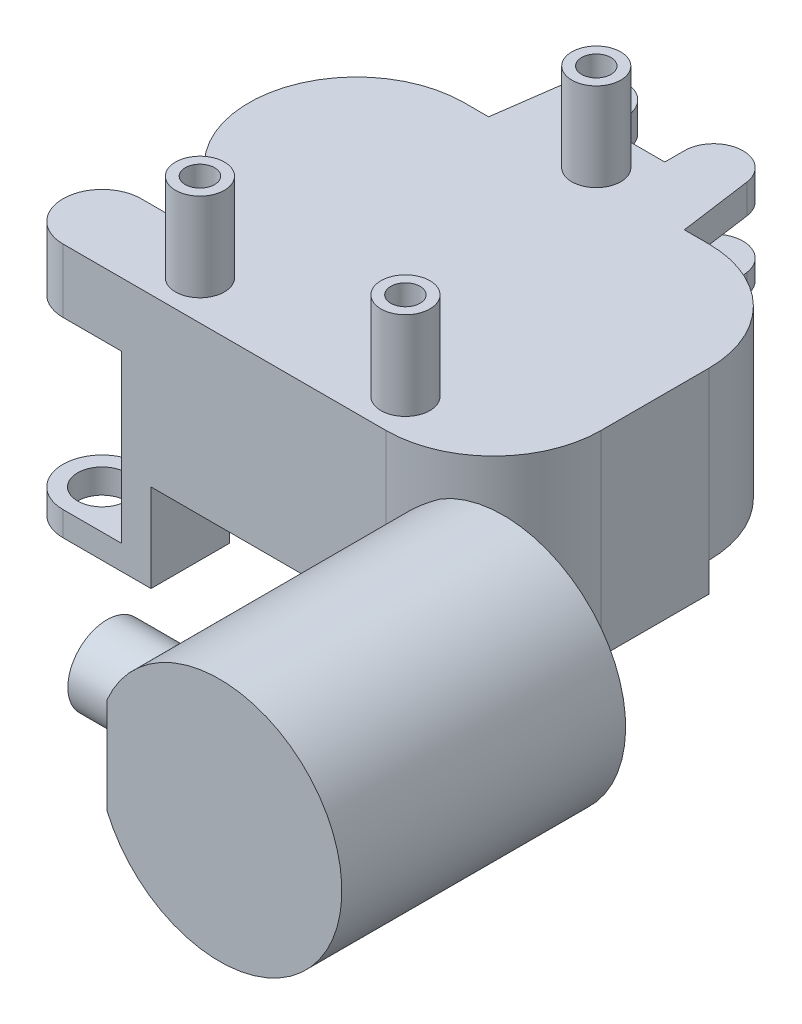
SolidWorks part; units mm, degrees
ref_plane "Front Plane" through (0, 0, 0) normal (0, 0, 1) x (1, 0, 0)
ref_plane "Top Plane" through (0, 0, 0) normal (0, 1, 0) x (1, 0, 0)
ref_plane "Right Plane" through (0, 0, 0) normal (1, 0, 0) x (0, 0, -1)
sketch "Sketch1" plane through (0, 0, 0) normal (0, 1, 0) x (1, 0, 0)
  line L0 (0, 0) -> (-101.2967, 0) construction
  line L6 (-11, 16.5) -> (-36, 16.5)
  line L7 (-41, -4.298) -> (-41, -16.5)
  line L8 (-41, -16.5) -> (-11, -16.5)
  line L10 (0, -5.5) -> (0, 5.5)
  arc A5 (0, 5.5) -> (-11, 16.5) centre (-11, 5.5) ccw
  arc A6 (-36, 16.5) -> (-41, -4.298) centre (-36, 5.5) ccw
  arc A7 (-11, -16.5) -> (0, -5.5) centre (-11, -5.5) ccw
  point P13 (0, 0)
  dimension "D1" = 11
  dimension "D4" = 41
  dimension "D5" = 11
  dimension "D2" = 36
  dimension "D3" = 33
extrude "Boss-Extrude1" add sketch "Sketch1" along normal blind 17
sketch "Sketch2" plane through (0, 17, 0) normal (0, 1, 0) x (1, 0, 0)
  line L0 (-33.5, 16.5) -> (-32.4715, 23.9123)
  line L2 (-26.5, 23.5) -> (-26.5, 21.5)
  line L3 (-26.5, 21.5) -> (-20.5, 21.5)
  line L4 (-20.5, 21.5) -> (-20.5, 23.5)
  line L5 (-14.5285, 23.9123) -> (-13.5, 16.5)
  line L6 (-33.5, 16.5) -> (-13.5, 16.5)
  line L10 (-11, 16.5) -> (-36, 16.5) construction
  arc A0 (-32.4715, 23.9123) -> (-26.5, 23.5) centre (-29.5, 23.5) cw
  arc A1 (-20.5, 23.5) -> (-14.5285, 23.9123) centre (-17.5, 23.5) cw
  point P3 (-23.5, 16.5)
  point P25 (-23.5, 21.5)
  dimension "D1" = 3
  dimension "D2" = 2
  dimension "D3" = 5
  dimension "D4" = 6
  dimension "D5" = 20
  dimension "D6" = 13.5
extrude "Boss-Extrude2" add sketch "Sketch2" against normal blind 10
ref_plane "Plane1" through (0, 0, 44.5) normal (0, 0, 1) x (1, 0, 0)
sketch "Sketch5" plane through (0, 0, 44.5) normal (0, 0, 1) x (1, 0, 0)
  line L0 (0, 17) -> (-11, 17) construction
  line L1 (-11.5, 6.899) -> (-11.5, -2.899)
  arc A0 (-11.5, -2.899) -> (-11.5, 6.899) centre (0, 2) ccw
  dimension "D2" = 12.5
  dimension "D1" = 15
  dimension "D3" = 11.5
extrude "Boss-Extrude3" add sketch "Sketch5" against normal blind 29
sketch "Sketch6" plane through (-11.5, 0, 0) normal (-1, 0, 0) x (0, 0, 1)
  line L0 (44.5, 6.899) -> (44.5, -2.899) construction
  line L4 (18.0627, 2) -> (42.4878, 2) construction
  line L5 (15.5, -10.5) -> (44.5, -10.5) construction
  line L6 (44.5, 14.5) -> (15.5, 14.5) construction
  circle A0 centre (36.5, 2) radius 4
  dimension "D1" = 8
  dimension "D2" = 8
extrude "Boss-Extrude4" add sketch "Sketch6" along normal blind 8
sketch "Sketch7" plane through (0, 17, 0) normal (0, 1, 0) x (1, 0, 0)
  line L0 (-44, -8.5) -> (-35, -8.5)
  line L2 (-35, -16.5) -> (-44, -16.5)
  line L3 (-35, -8.5) -> (-35, -16.5)
  line L4 (-41, -4.298) -> (-41, -16.5) construction
  line L5 (-41, -16.5) -> (-11, -16.5) construction
  arc A0 (-44, -8.5) -> (-44, -16.5) centre (-44, -12.5) ccw
  dimension "D1" = 4
  dimension "D3" = 3
  dimension "D2" = 13
extrude "Boss-Extrude5" add sketch "Sketch7" against normal blind 26
sketch "Sketch11" plane through (0, 17, 0) normal (0, 1, 0) x (1, 0, 0)
  line L0 (-11, 16.5) -> (-13.5, 16.5) construction
  line L1 (-23.5, 27.1588) -> (-23.5, -9.7895) construction
  circle A0 centre (-23.5, 17.5) radius 2.5
  circle A1 centre (-34, -12.5) radius 2.5
  circle A2 centre (-13, -12.5) radius 2.5
  dimension "D2" = 30
  dimension "D3" = 21
  dimension "D4" = 5
  dimension "D1" = 1
extrude "Boss-Extrude6" add sketch "Sketch11" along normal blind 9
sketch "Sketch13" plane through (0, 0, 0) normal (0, -1, 0) x (1, 0, 0)
  line L0 (-11, -5.5) -> (0, -5.5)
  line L1 (0, -5.5) -> (0, 5.5)
  arc A0 (0, 5.5) -> (-11, -5.5) centre (-11, 5.5) ccw
extrude "Boss-Extrude8" add sketch "Sketch13" along normal blind 3
sketch "Sketch9" plane through (0, 0, 0) normal (0, -1, 0) x (1, 0, 0)
  line L0 (-25, -16.5) -> (-25, -5.5)
  line L1 (-11, -16.5) -> (-36, -16.5) construction
  line L2 (-25, -16.5) -> (-36, -16.5)
  arc A0 (-25, -5.5) -> (-36, -16.5) centre (-36, -5.5) ccw
extrude "Cut-Extrude1" cut sketch "Sketch9" against normal blind 3
sketch "Sketch12" plane through (0, 0, 0) normal (0, -1, 0) x (1, 0, 0)
  circle A0 centre (-36, -5.5) radius 5
  dimension "D1" = 10
extrude "Boss-Extrude7" add sketch "Sketch12" against normal blind 5 draft 45 from offset 2 draft outward yes
sketch "Sketch10" plane through (0, 0, 16.5) normal (0, 0, 1) x (1, 0, 0)
  line L1 (-48, 10.5) -> (-38, 10.5)
  line L2 (-48, 10.5) -> (-48, -6.5)
  line L3 (-48, -6.5) -> (-38, -6.5)
  line L4 (-38, 10.5) -> (-38, -6.5)
  line L6 (-48, 17) -> (-48, -9) construction
  line L7 (-44, 17) -> (-11, 17) construction
  line L8 (-48, -9) -> (-44, -9) construction
  dimension "D1" = 6.5
  dimension "D2" = 2.5
  dimension "D3" = 10
extrude "Cut-Extrude2" cut sketch "Sketch10" against normal blind 9.2
sketch "Sketch14" plane through (0, 0, 0) normal (1, 0, 0) x (0, 0, -1)
  line L1 (26.5, 9) -> (1.5, 9)
  line L2 (26.5, 9) -> (26.5, 14)
  line L3 (26.5, 14) -> (1.5, 14)
  line L4 (1.5, 9) -> (1.5, 14)
  line L5 (26.5, 9) -> (1.5, 14) construction
  line L6 (26.5, 14) -> (1.5, 9) construction
  line L7 (16.5, 17) -> (23.9123, 17) construction
  line L9 (26.5, 7) -> (26.5, 17) construction
  point P0 (14, 11.5)
  dimension "D1" = 3
  dimension "D2" = 5
  dimension "D3" = 25
extrude "Cut-Extrude3" cut sketch "Sketch14" against normal through all from vertex starting at point (-13.5, 7, -16.5)
sketch "Sketch15" plane through (-19.5, 0, 0) normal (-1, 0, 0) x (0, 0, 1)
  circle A0 centre (36.5, 2) radius 2.5
  dimension "D1" = 5
extrude "Cut-Extrude4" cut sketch "Sketch15" against normal up to surface (8 mm away) contours A0 up to face at (-11.5, -2, 36.5)
sketch "Sketch16" plane through (0, 26, 0) normal (0, 1, 0) x (1, 0, 0)
  circle A0 centre (-23.5, 17.5) radius 1.5
  circle A1 centre (-34, -12.5) radius 1.5
  circle A2 centre (-13, -12.5) radius 1.5
  dimension "D1" = 3
extrude "Cut-Extrude5" cut sketch "Sketch16" against normal offset from surface (6 mm away) 3 up to face at (-13, 17, 15)
sketch "Sketch17" plane through (0, -9, 0) normal (0, -1, 0) x (1, 0, 0)
  circle A0 centre (-44, 12.5) radius 2.5
  dimension "D1" = 5
extrude "Cut-Extrude6" cut sketch "Sketch17" against normal blind 21.5
fillet "Fillet1" radius 6 1 edges at (-38, 5.25, 7.3)
